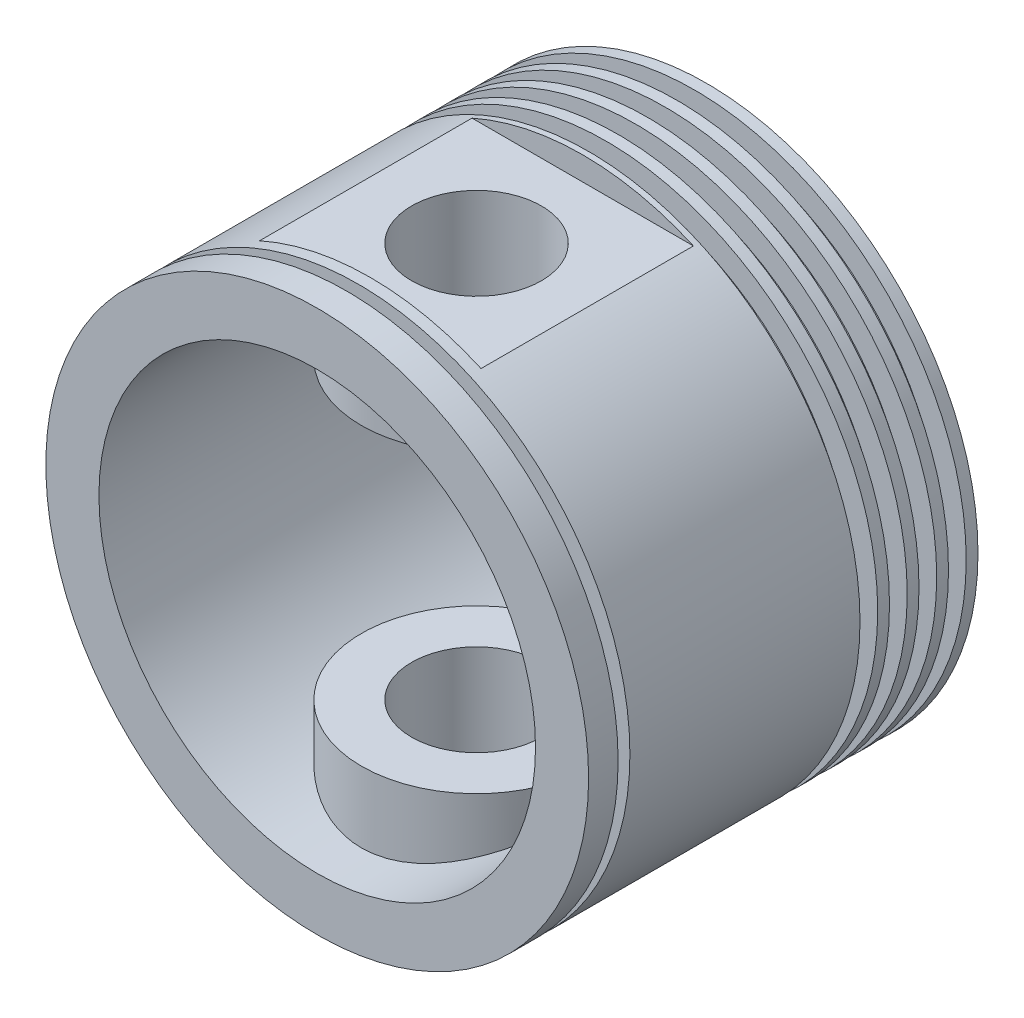
SolidWorks part; units mm, degrees
ref_plane "Front Plane" through (0, 0, 0) normal (0, 0, 1) x (1, 0, 0)
ref_plane "Top Plane" through (0, 0, 0) normal (0, 1, 0) x (1, 0, 0)
ref_plane "Right Plane" through (0, 0, 0) normal (1, 0, 0) x (0, 0, -1)
sketch "Sketch1" plane through (0, 0, 0) normal (0, 1, 0) x (1, 0, 0)
  line L0 (0, 0) -> (0, 41.3242) construction
  line L1 (0, 41.3242) -> (46, 41.3242)
  line L2 (46, 41.3242) -> (46, 39.3242)
  line L3 (46, 39.3242) -> (42, 39.3242)
  line L4 (42, 39.3242) -> (42, 36.3242)
  line L5 (42, 36.3242) -> (46, 36.3242)
  line L6 (46, 36.3242) -> (46, 34.3242)
  line L7 (46, 34.3242) -> (42, 34.3242)
  line L8 (42, 34.3242) -> (42, 31.3242)
  line L9 (42, 31.3242) -> (46, 31.3242)
  line L10 (46, 31.3242) -> (46, 29.3242)
  line L11 (46, 29.3242) -> (42, 29.3242)
  line L12 (42, 29.3242) -> (42, 26.3242)
  line L13 (42, 26.3242) -> (46, 26.3242)
  line L14 (46, 26.3242) -> (46, 24.3242)
  line L15 (46, 24.3242) -> (42, 24.3242)
  line L16 (42, 24.3242) -> (42, 21.3242)
  line L17 (42, 21.3242) -> (46, 21.3242)
  line L18 (46, 21.3242) -> (46, -17.6758)
  line L19 (46, -17.6758) -> (42, -17.6758)
  line L20 (42, -17.6758) -> (42, -19.6758)
  line L21 (42, -19.6758) -> (46, -19.6758)
  line L22 (46, -19.6758) -> (46, -24.6758)
  line L23 (46, -24.6758) -> (37, -24.6758)
  line L25 (37, 37.3242) -> (0, 37.3242)
  line L26 (0, 37.3242) -> (0, 41.3242)
  line L30 (37, 37.3242) -> (37, 22.8587)
  line L34 (37, 22.8587) -> (37, -24.6758)
  dimension "D2" = 46
  dimension "D3" = 4
  dimension "D4" = 4
  dimension "D5" = 4
  dimension "D6" = 4
  dimension "D7" = 4
  dimension "D8" = 4
  dimension "D9" = 4
  dimension "D10" = 4
  dimension "D11" = 4
  dimension "D13" = 66
  dimension "D14" = 2
  dimension "D15" = 3
  dimension "D16" = 2
  dimension "D17" = 3
  dimension "D18" = 2
  dimension "D19" = 3
  dimension "D20" = 2
  dimension "D21" = 3
  dimension "D22" = 46
  dimension "D23" = 37
  dimension "D24" = 37
  dimension "D25" = 62
  dimension "D26" = 39
  dimension "D27" = 2
  dimension "D28" = 7
revolve "Revolve1" add sketch "Sketch1" angle 360 about L0
ref_plane "Plane1" through (0, 25, 0) normal (0, 1, 0) x (1, 0, 0)
sketch "Sketch2" plane through (0, 25, 0) normal (0, 1, 0) x (1, 0, 0)
  line L1 (-46, -24.6758) -> (46, -24.6758) construction
  circle A0 centre (0, 2.3242) radius 19.5
  dimension "D1" = 39
  dimension "D2" = 27
extrude "Boss-Extrude1" add sketch "Sketch2" along normal up to next
mirror "Mirror1" about plane through (0, 0, 0) normal (0, 1, 0) of "Boss-Extrude1"
sketch "Sketch3" plane through (0, 0, 0) normal (0, 1, 0) x (1, 0, 0)
  line L0 (-46, -24.6758) -> (46, -24.6758) construction
  circle A0 centre (0, 2.3242) radius 11
  dimension "D2" = 22
  dimension "D3" = 27
extrude "Cut-Extrude2" cut sketch "Sketch3" against normal through all both and the other way through all
sketch "Sketch7" plane through (0, 0, 0) normal (1, 0, 0) x (0, 0, -1)
  line L1 (-15.6758, 50) -> (20.3242, 50)
  line L2 (-15.6758, 50) -> (-15.6758, 42)
  line L3 (-15.6758, 42) -> (20.3242, 42)
  line L4 (20.3242, 50) -> (20.3242, 42)
  line L5 (-15.6758, 50) -> (20.3242, 42) construction
  line L6 (-15.6758, 42) -> (20.3242, 50) construction
  line L7 (-24.6758, 46) -> (-24.6758, -46) construction
  point P0 (2.3242, 46)
  dimension "D1" = 27
  dimension "D2" = 36
  dimension "D3" = 8
extrude "Cut-Extrude4" cut sketch "Sketch7" against normal through all both and the other way through all
mirror "Mirror2" about plane through (0, 0, 0) normal (0, 1, 0) of "Cut-Extrude4"
ref_axis "Axis1" through (0, 0, -20.2807) along (0, 0, 1)
